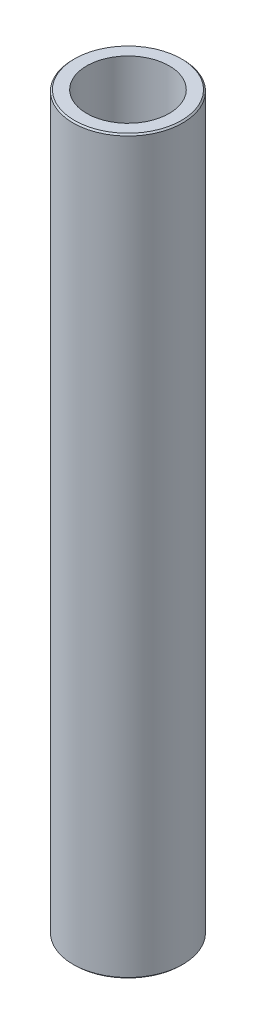
SolidWorks part; units mm, degrees
ref_plane "Front Plane" through (0, 0, 0) normal (0, 0, 1) x (1, 0, 0)
ref_plane "Top Plane" through (0, 0, 0) normal (0, 1, 0) x (1, 0, 0)
ref_plane "Right Plane" through (0, 0, 0) normal (1, 0, 0) x (0, 0, -1)
sketch "Sketch1" plane through (0, 0, 0) normal (0, 1, 0) x (1, 0, 0)
  circle A0 centre (0, 0) radius 45
  dimension "SHAFT_OD" = 90
extrude "Boss-Extrude1" add sketch "Sketch1" along normal blind 600
sketch "Sketch2" plane through (0, 0, 0) normal (0, 1, 0) x (1, 0, 0)
  circle A0 centre (0, 0) radius 33.8356
  dimension "BORE_D" = 67.6712
extrude "Cut-Extrude1" cut sketch "Sketch2" along normal through all
chamfer "Chamfer1" distance 1.1664 angle 45 2 edges at (0, 600, 45) (0, 0, 45)
